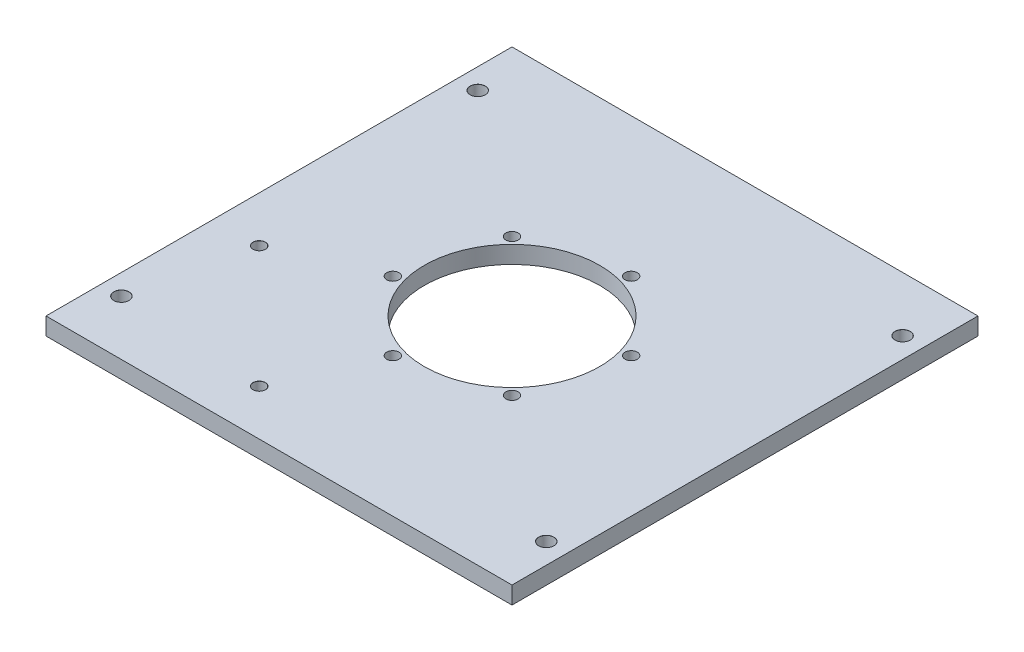
SolidWorks part; units mm, degrees
material "6061 Alloy"
ref_plane "Front Plane" through (0, 0, 0) normal (0, 0, 1) x (1, 0, 0)
ref_plane "Top Plane" through (0, 0, 0) normal (0, 1, 0) x (1, 0, 0)
ref_plane "Right Plane" through (0, 0, 0) normal (1, 0, 0) x (0, 0, -1)
sketch "Sketch1" plane through (0, 0, 0) normal (0, 1, 0) x (1, 0, 0)
  line L1 (-85, -85) -> (85, -85)
  line L2 (-85, -85) -> (-85, 85)
  line L3 (-85, 85) -> (85, 85)
  line L4 (85, -85) -> (85, 85)
  line L5 (-85, -85) -> (85, 85) construction
  line L6 (-85, 85) -> (85, -85) construction
  circle A1 centre (0, 0) radius 39.5
  arc A5 (-25.1023, 25.1023) -> (9.1881, 34.2904) centre (0, 0) cw
  arc A7 (9.1881, 34.2904) -> (-34.2904, -9.1881) centre (0, 0) ccw
  arc A9 (-34.2904, -9.1881) -> (-9.1881, -34.2904) centre (0, 0) ccw
  arc A11 (-9.1881, -34.2904) -> (25.1023, -25.1023) centre (0, 0) ccw
  circle A13 centre (0, 0) radius 32
  arc A14 (25.1023, -25.1023) -> (34.2904, 9.1881) centre (0, 0) ccw
extrude "Boss-Extrude3" add sketch "Sketch1" along normal blind 6.35 contours L1 L4 L3 L2 A1 | A1 A13 region at (-82.5958, 0, 0) region at (-38.3828, 0, 0)
hole_wizard "M4 Clearance Hole2" positions "Sketch6" profile "Sketch7" hole size "M4" standard "ANSI Metric" end condition through all
sketch "Sketch6" plane through (0, 0, 0) normal (0, -1, 0) x (-1, 0, 0)
  point P0 (-9.1881, 34.2904)
  point P3 (25.1023, 25.1023)
  point P6 (34.2904, -9.1881)
  point P9 (9.1881, -34.2904)
  point P12 (-25.1023, -25.1023)
  point P15 (-34.2904, 9.1881)
sketch "Sketch7" plane through (9.1881, 0, -34.2904) normal (1, 0, 0) x (0, 0, -1)
  line L0 (0, 0) -> (0, 6.35)
  line L1 (0, 6.35) -> (2.25, 6.35)
  line L2 (2.25, 6.35) -> (2.25, 0.025)
  line L3 (2.25, 0.025) -> (2.275, 0)
  line L5 (2.275, 0) -> (0, 0)
  line L6 (-2.25, 0.025) -> (-2.275, 0) construction
  line L11 (0, -6.35) -> (0, 107.95) construction
  dimension "Thru Hole Dia." = 4.5
  dimension "Thru Hole Depth" = 6.35
  dimension "Near C'Sink Dia." = 4.55
  dimension "Near C'Sink Angle" = 90
sketch "Sketch13" plane through (0, 6.35, 0) normal (0, 1, 0) x (1, 0, 0)
  line L0 (-85, -85) -> (-46.1091, -46.1091)
  line L1 (-46.1091, -46.1091) -> (-68.3017, -23.9166)
  line L2 (-46.1091, -46.1091) -> (-23.9166, -68.3017)
hole_wizard "M4 Clearance Hole5" positions "Sketch14" profile "Sketch15" hole size "M4" standard "ANSI Metric" end condition through all
sketch "Sketch14" plane through (0, 6.35, 0) normal (0, 1, 0) x (1, 0, 0)
  point P0 (-68.3017, -23.9166)
  point P3 (-23.9166, -68.3017)
sketch "Sketch15" plane through (-68.3017, 6.35, 23.9166) normal (1, 0, 0) x (0, 0, 1)
  line L0 (0, 0) -> (0, 6.35)
  line L1 (0, 6.35) -> (2.25, 6.35)
  line L2 (2.25, 6.35) -> (2.25, 0.025)
  line L3 (2.25, 0.025) -> (2.275, 0)
  line L5 (2.275, 0) -> (0, 0)
  line L6 (-2.25, 0.025) -> (-2.275, 0) construction
  line L11 (0, -6.35) -> (0, 107.95) construction
  dimension "Thru Hole Dia." = 4.5
  dimension "Thru Hole Depth" = 6.35
  dimension "Near C'Sink Dia." = 4.55
  dimension "Near C'Sink Angle" = 90
sketch "Sketch16" plane through (0, 6.35, 0) normal (0, 1, 0) x (1, 0, 0)
  line L0 (-85, -85) -> (-55, -85)
  line L1 (-85, -85) -> (85, -85) construction
  line L2 (-55, -85) -> (-55, -70)
  line L3 (-85, -85) -> (-75, -85)
  line L4 (-75, -85) -> (-75, -70)
  line L5 (-75, -70) -> (-55, -70)
  line L6 (-85, 85) -> (-55, 85)
  line L7 (-85, 85) -> (85, 85) construction
  line L8 (85, 85) -> (55, 85)
  line L9 (85, -85) -> (55, -85)
  line L11 (-55, 85) -> (-75, 85)
  line L12 (-55, 85) -> (-55, 70)
  line L13 (-55, 70) -> (-75, 70)
  line L14 (-75, 85) -> (-75, 70)
  line L15 (55, 85) -> (75, 85)
  line L16 (55, 85) -> (55, 70)
  line L17 (55, 70) -> (75, 70)
  line L18 (75, 85) -> (75, 70)
  line L19 (55, -85) -> (75, -85)
  line L20 (55, -85) -> (55, -70)
  line L21 (55, -70) -> (75, -70)
  line L22 (75, -85) -> (75, -70)
sketch "Sketch23" plane through (0, 6.35, 0) normal (0, 1, 0) x (1, 0, 0)
  line L0 (-85, -85) -> (-85, -55)
  line L1 (-85, -85) -> (-85, 85) construction
  line L2 (-85, 85) -> (-85, 55)
  line L3 (85, 85) -> (85, 55)
  line L4 (-85, 85) -> (85, 85) construction
  line L5 (85, -85) -> (85, 85) construction
  line L6 (85, -85) -> (85, -55)
  line L8 (-85, 55) -> (-70, 55)
  line L9 (-85, 55) -> (-85, 75)
  line L10 (-85, 75) -> (-70, 75)
  line L11 (-70, 55) -> (-70, 75)
  line L12 (85, 55) -> (70, 55)
  line L13 (85, 55) -> (85, 75)
  line L14 (85, 75) -> (70, 75)
  line L15 (70, 55) -> (70, 75)
  line L16 (85, -55) -> (70, -55)
  line L17 (85, -55) -> (85, -75)
  line L18 (85, -75) -> (70, -75)
  line L19 (70, -55) -> (70, -75)
  line L20 (-85, -55) -> (-70, -55)
  line L21 (-85, -55) -> (-85, -75)
  line L22 (-85, -75) -> (-70, -75)
  line L23 (-70, -55) -> (-70, -75)
hole_wizard "M5 Clearance Hole1" positions "Sketch24" profile "Sketch25" hole size "M5" standard "ANSI Metric" end condition through all
sketch "Sketch24" plane through (0, 6.35, 0) normal (0, 1, 0) x (1, 0, 0)
  point P0 (-77.5, 65)
  point P2 (77.5, 65)
  point P4 (77.5, -65)
  point P6 (-77.5, -65)
sketch "Sketch25" plane through (-77.5, 6.35, -65) normal (1, 0, 0) x (0, 0, 1)
  line L0 (0, 0) -> (0, 6.35)
  line L1 (0, 6.35) -> (2.75, 6.35)
  line L2 (2.75, 6.35) -> (2.75, 0.025)
  line L3 (2.75, 0.025) -> (2.775, 0)
  line L5 (2.775, 0) -> (0, 0)
  line L6 (-2.75, 0.025) -> (-2.775, 0) construction
  line L11 (0, -6.35) -> (0, 107.95) construction
  dimension "Thru Hole Dia." = 5.5
  dimension "Thru Hole Depth" = 6.35
  dimension "Near C'Sink Dia." = 5.55
  dimension "Near C'Sink Angle" = 90
